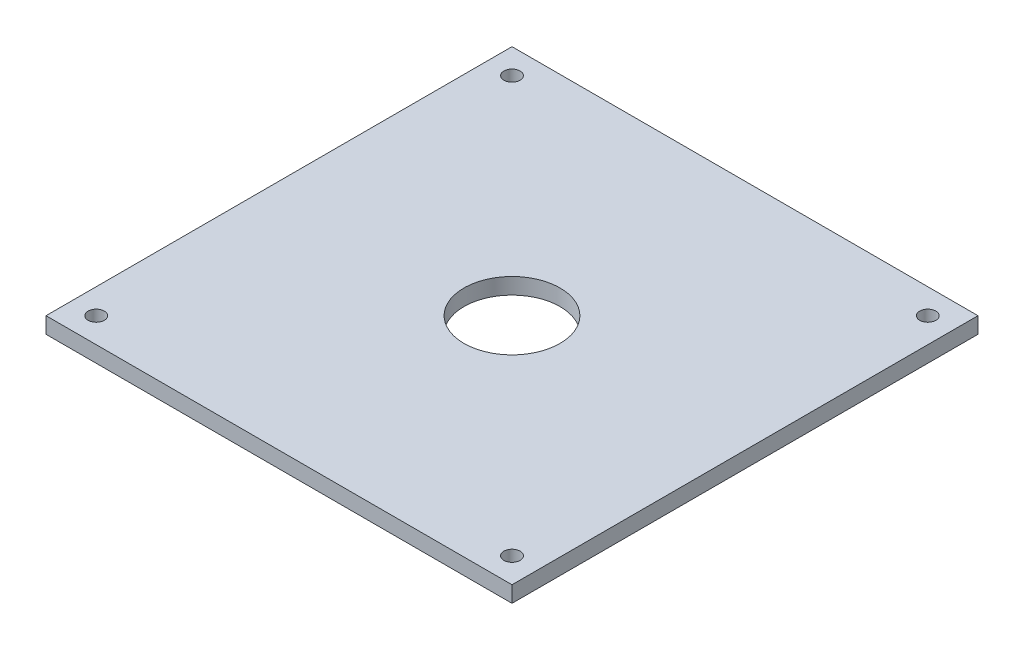
SolidWorks part; units mm, degrees
ref_plane "Front Plane" through (0, 0, 0) normal (0, 0, 1) x (1, 0, 0)
ref_plane "Top Plane" through (0, 0, 0) normal (0, 1, 0) x (1, 0, 0)
ref_plane "Right Plane" through (0, 0, 0) normal (1, 0, 0) x (0, 0, -1)
sketch "Sketch1" plane through (0, 0, 0) normal (0, 1, 0) x (1, 0, 0)
  line L1 (0, 0) -> (130, 0)
  line L2 (0, 0) -> (0, 130)
  line L3 (0, 130) -> (130, 130)
  line L4 (130, 0) -> (130, 130)
  circle A0 centre (65, 65) radius 13.4
  circle A1 centre (123, 123) radius 2.25
  circle A2 centre (65, 65) radius 59.6241 construction
  circle A3 centre (123, 7) radius 2.25
  circle A4 centre (7, 7) radius 2.25
  circle A5 centre (7, 123) radius 2.25
  dimension "D3" = 26.8
  dimension "D4" = 4.5
  dimension "D1" = 130
  dimension "D2" = 130
  dimension "D5" = 7
  dimension "D6" = 7
  dimension "D7" = 65
  dimension "D8" = 65
  dimension "D9" = 4
extrude "Boss-Extrude1" add sketch "Sketch1" along normal blind 4.5
equation "\"D1@Boss-Extrude1\"=\"mat@v5.assembly\""
